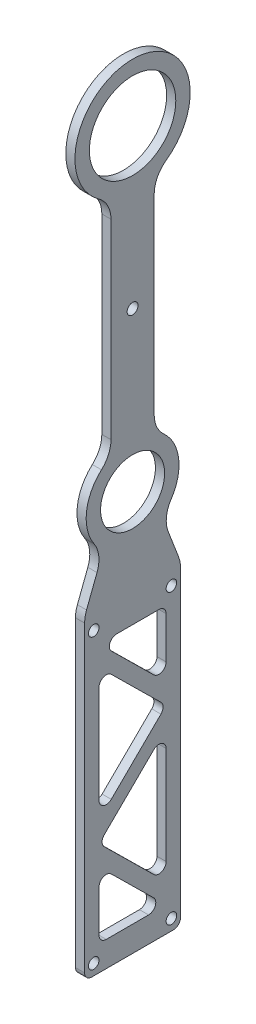
SolidWorks part; units mm, degrees
material "6061 Alloy"
ref_plane "Front Plane" through (0, 0, 0) normal (0, 0, 1) x (1, 0, 0)
ref_plane "Top Plane" through (0, 0, 0) normal (0, 1, 0) x (1, 0, 0)
ref_plane "Right Plane" through (0, 0, 0) normal (1, 0, 0) x (0, 0, -1)
sketch "Sketch1" plane through (0, 0, 0) normal (1, 0, 0) x (0, 0, -1)
  line L0 (-13.4747, 0) -> (13.4747, 0) construction
  line L1 (0, 0) -> (0, 35) construction
  line L2 (-13.4747, 0) -> (0, 35) construction
  line L3 (0, 35) -> (13.4747, 0) construction
  line L4 (13.4747, 0) -> (-13.4747, 0) construction
  line L5 (20.7574, -5) -> (-20.7574, -5)
  line L6 (-20.7574, -5) -> (-10.1693, 22.5021)
  line L7 (0, 48.9165) -> (1.1006, 46.0579) construction
  line L8 (0, 35) -> (0, 46.1125) construction
  line L9 (0, 35) -> (0, 46.1125) construction
  line L12 (-7.5, 35) -> (-7.5, 43.1999) construction
  line L13 (7.5, 35) -> (7.5, 43.1999) construction
  line L14 (-7.5, 35) -> (-7.5, 29.4356) construction
  line L15 (7.5, 35) -> (7.5, 29.4356) construction
  line L16 (-13.4747, 0) -> (13.4747, 0) construction
  line L17 (-13.4747, 0) -> (-13.4747, -100) construction
  line L18 (13.4747, 0) -> (13.4747, -100) construction
  line L19 (-13.4747, -100) -> (13.4747, -100) construction
  line L20 (-20.7574, -5) -> (20.7574, -5)
  line L21 (-20.7574, -5) -> (-20.7574, -103.81)
  line L22 (20.7574, -5) -> (20.7574, -103.81)
  line L23 (-20.7574, -103.81) -> (20.7574, -103.81)
  line L24 (-10.1693, 22.5021) -> (-8.2317, 27.535) construction
  line L25 (-7.5, 29.4356) -> (-6.6746, 31.5795) construction
  line L26 (-20.7574, -5) -> (0, 48.9165) construction
  line L27 (8.2317, 27.535) -> (10.1693, 22.5021) construction
  line L28 (10.1693, 22.5021) -> (20.7574, -5)
  line L29 (0, 48.9165) -> (20.7574, -5) construction
  line L30 (-7.5, 43.1999) -> (-7.5, 49.2605) construction
  line L31 (-7.5, 49.2605) -> (-7.5, 145)
  line L32 (7.5, 43.1999) -> (7.5, 49.2605) construction
  line L33 (7.5, 49.2605) -> (7.5, 145)
  line L34 (-8.2317, 27.535) -> (-7.5, 29.4356) construction
  line L35 (-6.6746, 31.5795) -> (-1.1006, 46.0579) construction
  line L36 (-1.1006, 46.0579) -> (0, 48.9165) construction
  line L37 (1.1006, 46.0579) -> (6.6746, 31.5795) construction
  line L38 (6.6746, 31.5795) -> (7.5, 29.4356) construction
  line L39 (7.5, 29.4356) -> (8.2317, 27.535) construction
  line L40 (0, 46.1125) -> (0, 48.9165) construction
  line L41 (0, 48.9165) -> (0, 145) construction
  line L42 (0, 46.1125) -> (0, 48.9165) construction
  line L43 (0, 48.9165) -> (0, 145) construction
  circle A0 centre (-13.4747, 0) radius 1.8288
  circle A1 centre (0, 35) radius 11.1125
  circle A2 centre (13.4747, 0) radius 1.8288
  circle A3 centre (0, 145) radius 3 construction
  arc A6 (-7.5, 35) -> (-6.6746, 31.5795) centre (0, 35) ccw construction
  arc A7 (7.5, 145) -> (-7.5, 145) centre (0, 145) ccw
  circle A8 centre (-13.4747, -100) radius 1.8288
  circle A9 centre (13.4747, -100) radius 1.8288
  circle A17 centre (0, 145) radius 15
  circle A18 centre (0, 145) radius 20
  arc A19 (10.1693, 22.5021) -> (7.5, 49.2605) centre (0, 35) ccw
  arc A20 (-10.1693, 22.5021) -> (-5.789, 19.9634) centre (0, 35) ccw construction
  circle A21 centre (0, 35) radius 16.1125 construction
  arc A22 (-5.789, 19.9634) -> (0, 18.8875) centre (0, 35) ccw construction
  arc A23 (0, 18.8875) -> (5.789, 19.9634) centre (0, 35) ccw construction
  arc A24 (5.789, 19.9634) -> (10.1693, 22.5021) centre (0, 35) ccw construction
  arc A25 (0, 51.1125) -> (-7.5, 49.2605) centre (0, 35) ccw construction
  arc A26 (-7.5, 49.2605) -> (-10.1693, 22.5021) centre (0, 35) ccw
  arc A27 (7.5, 49.2605) -> (0, 51.1125) centre (0, 35) ccw construction
  arc A28 (6.6746, 31.5795) -> (7.5, 35) centre (0, 35) ccw construction
  arc A29 (2.6946, 28.0008) -> (6.6746, 31.5795) centre (0, 35) ccw construction
  arc A30 (0, 27.5) -> (2.6946, 28.0008) centre (0, 35) ccw construction
  arc A31 (-2.6946, 28.0008) -> (0, 27.5) centre (0, 35) ccw construction
  arc A32 (-6.6746, 31.5795) -> (-2.6946, 28.0008) centre (0, 35) ccw construction
  point P4 (0, 0)
  point P14 (0, 90)
  point P34 (0, 145)
  dimension "D3" = 3.6576
  dimension "D4" = 22.225
  dimension "D7" = 6
  dimension "D11" = 5
  dimension "D13" = 30
  dimension "D14" = 40
  dimension "D1" = 26.9494
  dimension "D5" = 110
  dimension "D6" = 15
  dimension "D8" = 100
  dimension "D9" = 3.81
  dimension "D10" = 35
  dimension "D2" = 5
extrude "Boss-Extrude1" add sketch "Sketch1" along normal blind 3.175 contours L21 L23 L22 L5 A9 A8 | A6 L6 L5 L7 A2 A0 | L6 A6 L7 A1 | A18 L12 A6 L6 L7 L13 | A6 L7 L15 | A6 L14 L6 | L12 A18 L13 A17 | L13 A18 L12 A17 region at (0, -54.1702, 0) region at (0, 51.0281, 0) region at (0, 128.0809, 0) region at (0, 129.2346, -8.0555)
sketch "Sketch2" plane through (3.175, 0, 0) normal (1, 0, 0) x (0, 0, -1)
  line L0 (-11.645, -5) -> (11.645, -5) construction
  line L1 (-11.645, -95) -> (11.645, -95) construction
  line L2 (11.645, -95) -> (11.645, -5) construction
  line L3 (-11.645, -95) -> (-11.645, -5) construction
  line L6 (11.645, -38.5118) -> (-11.645, -61.4882) construction
  line L7 (11.645, -5) -> (-11.645, -5)
  line L8 (-11.645, -5) -> (11.645, -27.9764)
  line L9 (11.645, -27.9764) -> (11.645, -5)
  line L10 (-11.645, -12.0236) -> (11.645, -35)
  line L11 (11.645, -35) -> (-11.645, -57.9764)
  line L12 (-11.645, -57.9764) -> (-11.645, -35)
  line L13 (-11.645, -35) -> (-11.645, -12.0236)
  line L14 (-11.645, -72.0236) -> (-11.645, -95)
  line L15 (-11.645, -95) -> (11.645, -95)
  line L16 (11.645, -95) -> (-11.645, -72.0236)
  line L17 (11.645, -42.0236) -> (11.645, -65)
  line L18 (11.645, -65) -> (11.645, -87.9764)
  line L19 (11.645, -87.9764) -> (-11.645, -65)
  line L20 (-11.645, -65) -> (11.645, -42.0236)
  line L21 (16.645, -1056.0877) -> (16.645, 48943.9123) construction
  line L22 (-16.645, -1060.2922) -> (-16.645, 48939.7078) construction
  line L23 (16.645, 23.8875) -> (-16.645, 23.8875) construction
  line L24 (-20.7574, -103.81) -> (-16.645, -103.81)
  line L25 (-20.7574, -103.81) -> (-20.7574, 23.8875)
  line L26 (-16.645, -103.81) -> (-16.645, 23.8875)
  line L27 (-20.7574, 23.8875) -> (-16.645, 23.8875)
  line L28 (-20.7574, -103.81) -> (20.7574, -103.81) construction
  line L29 (20.7574, -103.81) -> (16.645, -103.81)
  line L30 (20.7574, -103.81) -> (20.7574, 23.8875)
  line L31 (16.645, -103.81) -> (16.645, 23.8875)
  line L32 (20.7574, 23.8875) -> (16.645, 23.8875)
  circle A0 centre (13.4747, 0) radius 1.8288 construction
  circle A1 centre (13.4747, -100) radius 1.8288 construction
  circle A2 centre (0, 35) radius 11.1125 construction
  point P6 (11.645, -50)
  point P10 (0, 23.8875)
  point P21 (0, -50)
  dimension "D1" = 33.29
  dimension "D2" = 5
  dimension "D3" = 5
  dimension "D4" = 5
  dimension "D5" = 5
  dimension "D6" = 2.5
  dimension "D8" = 5
  dimension "D7" = 2
extrude "Cut-Extrude1" cut sketch "Sketch2" against normal up to next
fillet "Fillet3" radius 2.5 14 edges at (1.5875, -57.9764, 11.645) (1.5875, -35, -11.645) (1.5875, -95, -11.645) (1.5875, -72.0236, 11.645) (1.5875, -95, 11.645) (1.5875, -27.9764, -11.645) (1.5875, -5, -11.645) (1.5875, -12.0236, 11.645) (1.5875, -5, 11.645) (1.5875, -87.9764, -11.645) (1.5875, -42.0236, -11.645) (1.5875, -65, 11.645) (1.5875, -103.81, -16.645) (1.5875, -103.81, 16.645)
fillet "Fillet4" radius 10 8 edges at (1.5875, 5.6818, 16.645) (1.5875, 5.6818, -16.645) (1.5875, 126.4595, 7.5) (1.5875, 126.4595, -7.5) (1.5875, 49.2605, -7.5) (1.5875, 49.2605, 7.5) (1.5875, 22.5021, 10.1693) (1.5875, 22.5021, -10.1693)
hole_wizard "#6 Clearance Hole1" positions "Sketch3" profile "Sketch4" hole size "#6" standard "ANSI Inch" end condition up to next
sketch "Sketch3" plane through (3.175, 0, 0) normal (1, 0, 0) x (0, 0, -1)
  circle A0 centre (0, 35) radius 11.1125 construction
  point P0 (0, 90)
  dimension "D1" = 55
sketch "Sketch4" plane through (3.175, 90, 0) normal (0, 1, 0) x (0, 0, -1)
  line L0 (0, 0) -> (0, 3.175)
  line L1 (0, 3.175) -> (1.8986, 3.175)
  line L2 (1.8986, 3.175) -> (1.8986, 0)
  line L5 (1.8986, 0) -> (0, 0)
  line L11 (0, -6.35) -> (0, 107.95) construction
  dimension "Thru Hole Dia." = 3.7973
  dimension "Thru Hole Depth" = 3.175
